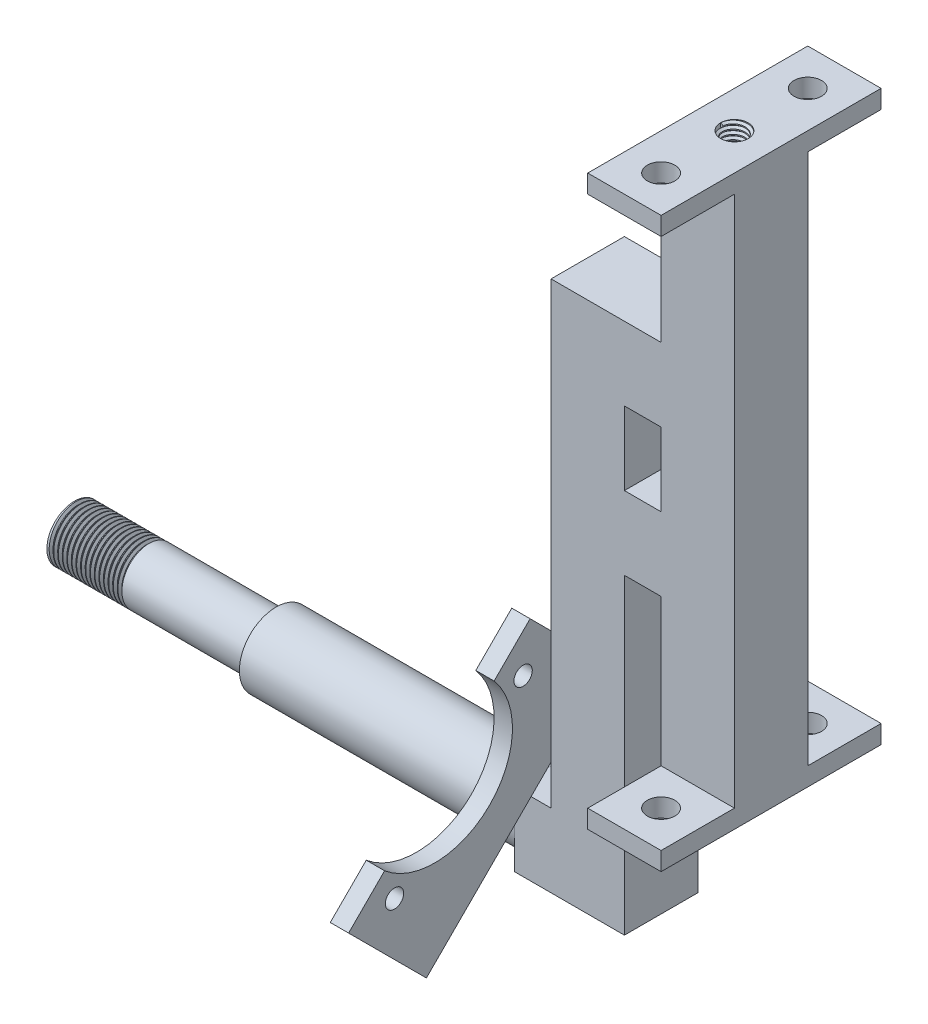
SolidWorks part; units mm, degrees
material "Plain Carbon Steel"
ref_plane "Front Plane" through (0, 0, 0) normal (0, 0, 1) x (1, 0, 0)
ref_plane "Top Plane" through (0, 0, 0) normal (0, 1, 0) x (1, 0, 0)
ref_plane "Right Plane" through (0, 0, 0) normal (1, 0, 0) x (0, 0, -1)
sketch "Sketch1" plane through (0, 0, 0) normal (0, 1, 0) x (1, 0, 0)
  line L1 (12.7, -12.7) -> (-12.7, -12.7)
  line L2 (12.7, -12.7) -> (12.7, 12.7)
  line L3 (12.7, 12.7) -> (-12.7, 12.7)
  line L4 (-12.7, -12.7) -> (-12.7, 12.7)
  line L5 (12.7, -12.7) -> (-12.7, 12.7) construction
  line L6 (12.7, 12.7) -> (-12.7, -12.7) construction
  line L7 (10.16, -10.16) -> (-10.16, -10.16)
  line L8 (10.16, -10.16) -> (10.16, 10.16)
  line L9 (10.16, 10.16) -> (-10.16, 10.16)
  line L10 (-10.16, -10.16) -> (-10.16, 10.16)
  line L11 (10.16, -10.16) -> (-10.16, 10.16) construction
  line L12 (10.16, 10.16) -> (-10.16, -10.16) construction
  point P0 (0, 0)
  point P5 (0, 0)
  dimension "D1" = 2.54
  dimension "1" = 25.4
extrude "Sq_Tb Extrude" add sketch "Sketch1" along normal blind 196.85
sketch "Sketch3" plane through (0, 196.85, 0) normal (0, 1, 0) x (1, 0, 0)
  line L0 (12.7, -12.7) -> (12.7, 12.7) construction
  line L1 (10.16, -10.16) -> (-10.16, -10.16)
  line L2 (10.16, -10.16) -> (10.16, 10.16)
  line L3 (10.16, 10.16) -> (-10.16, 10.16)
  line L4 (-10.16, -10.16) -> (-10.16, 10.16)
  line L5 (10.16, -10.16) -> (-10.16, 10.16) construction
  line L6 (10.16, 10.16) -> (-10.16, -10.16) construction
  line L7 (-12.7, 12.7) -> (12.7, 12.7)
  line L8 (-12.7, 12.7) -> (-12.7, 38.1)
  line L9 (-12.7, 38.1) -> (12.7, 38.1)
  line L10 (12.7, 12.7) -> (12.7, 38.1)
  line L11 (-12.7, 12.7) -> (12.7, 38.1) construction
  line L12 (-12.7, 38.1) -> (12.7, 12.7) construction
  line L13 (0, 0) -> (12.7, 0) construction
  line L14 (-12.7, -38.1) -> (12.7, -12.7) construction
  line L15 (-12.7, -12.7) -> (12.7, -38.1) construction
  line L16 (12.7, -12.7) -> (12.7, -38.1)
  line L17 (-12.7, -38.1) -> (12.7, -38.1)
  line L18 (-12.7, -12.7) -> (-12.7, -38.1)
  line L19 (-12.7, -12.7) -> (12.7, -12.7)
  circle A0 centre (0, 0) radius 4.7625
  circle A1 centre (0, 25.4) radius 4.7625
  circle A2 centre (0, -25.4) radius 4.7625
  point P0 (0, 0)
  point P13 (0, 25.4)
  point P26 (0, -25.4)
  dimension "D1" = 9.525
  dimension "D3" = 50.8
  dimension "D2" = 25.4
extrude "End Caps" add sketch "Sketch3" against normal blind 6.35
ref_plane "Mid-Plane" through (0, 98.425, 0) normal (0, 1, 0) x (1, 0, 0)
mirror "End Cap Mirror" about plane through (0, 98.425, 0) normal (0, 1, 0) of "End Caps"
thread "Top Thread" pitch 1.5875 method extrude profile "Thread Profile1" start angle 0, offset 0, length 0, pitch 1.5875, diameter 9.525
ref_plane "Plane2" through (-4.7625, 196.85, 0) normal (0, 0, 1) x (-1, 0, 0)
sketch "Thread Profile1" plane through (-4.7625, 196.85, 0) normal (0, 0, 1) x (-1, 0, 0)
  line L0 (0, 0) -> (0, 1.5875) construction
  line L11 (0, 0) -> (0, 1.3891)
  line L12 (0, 1.3891) -> (-0.8593, 0.893)
  line L13 (-0.8593, 0.893) -> (-0.8593, 0.4961)
  line L15 (-0.8593, 0.4961) -> (0, 0)
  line L17 (-0.8593, 0.6945) -> (0, 0.6945) construction
  point P2 (0, 0)
  dimension "Pitch" = 1.5875
  dimension "Profile_Angle" = 60
  dimension "Profile_Land" = 0.3969
  dimension "Profile_Height" = 0.8593
thread "Bottom Thread" pitch 1.5875 method extrude profile "Thread Profile2" start angle 0, offset 0, length 0, pitch 1.5875, diameter 9.525
ref_plane "Plane3" through (4.7625, 0, 0) normal (0, 0, 1) x (1, 0, 0)
sketch "Thread Profile2" plane through (4.7625, 0, 0) normal (0, 0, 1) x (1, 0, 0)
  line L0 (0, 0) -> (0, 1.5875) construction
  line L11 (0, 0) -> (0, 1.3891)
  line L12 (0, 1.3891) -> (-0.8593, 0.893)
  line L13 (-0.8593, 0.893) -> (-0.8593, 0.4961)
  line L15 (-0.8593, 0.4961) -> (0, 0)
  line L17 (-0.8593, 0.6945) -> (0, 0.6945) construction
  point P2 (0, 0)
  dimension "Pitch" = 1.5875
  dimension "Profile_Angle" = 60
  dimension "Profile_Land" = 0.3969
  dimension "Profile_Height" = 0.8593
sketch "Sketch9" plane through (0, 0, 0) normal (0, 0, 1) x (1, 0, 0)
  line L1 (-12.7, 190.5) -> (-12.7, 6.35) construction
  line L11 (-25.4, -50.8) -> (-63.5, -50.8)
  line L12 (-63.5, -50.8) -> (-63.5, -25.4)
  line L13 (-63.5, -25.4) -> (-63.1415, -25.4)
  line L15 (-63.5, -38.1) -> (0, -38.1) construction
  line L16 (0, -38.1) -> (0, 0) construction
  line L24 (-25.4, -25.4) -> (-25.4, -50.8)
  line L27 (-25.4, 107.95) -> (-50.8, 107.95) construction
  line L28 (-50.8, 107.95) -> (-50.8, -25.4)
  line L29 (-50.8, 107.95) -> (-50.8, 133.35)
  line L30 (-50.8, 133.35) -> (-12.7, 133.35)
  line L31 (-12.7, 190.5) -> (-12.7, 6.35) construction
  line L32 (-25.4, 107.95) -> (-12.7, 107.95)
  line L33 (-25.4, 57.15) -> (-12.7, 57.15)
  line L34 (-25.4, 82.55) -> (-12.7, 82.55)
  line L35 (-19.05, 82.55) -> (-19.05, 57.15) construction
  line L36 (-25.4, 107.95) -> (-50.8, 133.35) construction
  line L37 (-63.1415, -25.4) -> (-50.8, -25.4)
  line L38 (-50.8, -25.4) -> (-25.4, -25.4) construction
  line L39 (-50.8, -25.4) -> (-25.4, -50.8) construction
  line L40 (-12.7, 133.35) -> (-12.7, 107.95)
  line L41 (12.7, 190.5) -> (-12.7, 190.5) construction
  line L42 (-12.7, 0) -> (12.7, 0) construction
  line L43 (-25.4, 107.95) -> (-25.4, 82.55)
  line L44 (-25.4, 57.15) -> (-25.4, -25.4)
  line L45 (-12.7, 82.55) -> (-12.7, 57.15)
  dimension "D1" = 25.4
  dimension "D2" = 50.8
  dimension "D3" = 25.4
  dimension "D4" = 57.15
  dimension "D5" = 57.15
  dimension "D6" = 50.8
  dimension "D8" = 38.1
extrude "Sq_Tb Angles" add sketch "Sketch9" along normal blind 12.7 and the other way blind 12.7 contours L13 L12 L11 region at (-37.0114, 42.9079, 0)
sketch "Sketch11" plane through (0, 0, 0) normal (0, 0, 1) x (1, 0, 0)
  line L0 (-63.5, -38.1) -> (-228.6, -38.1)
  line L1 (-63.5, -50.8) -> (-63.5, -25.4) construction
  line L2 (-228.6, -38.1) -> (-228.6, -28.575)
  line L3 (-228.6, -28.575) -> (-158.75, -28.575)
  line L4 (-158.75, -28.575) -> (-158.75, -25.4)
  line L5 (-158.75, -25.4) -> (-63.5, -25.4)
  line L6 (-63.5, -25.4) -> (-63.5, -38.1)
  dimension "D1" = 12.7
  dimension "D2" = 9.525
  dimension "D3" = 95.25
  dimension "D4" = 69.85
revolve "Wheel Rod" add sketch "Sketch11" angle 360 about L0
thread "Wheel Threads" pitch 1.5875 method cut profile "Thread Profile3" start angle 0, offset 0, length 25.4, pitch 1.5875, diameter 19.05
ref_plane "Plane4" through (-228.6, -38.1, -9.525) normal (0, -1, 0) x (0, 0, -1)
sketch "Thread Profile3" plane through (-228.6, -38.1, -9.525) normal (0, -1, 0) x (0, 0, -1)
  line L0 (0, 0) -> (0, 1.5875) construction
  line L11 (0, 0) -> (0, 1.3891)
  line L12 (0, 1.3891) -> (-0.8593, 0.893)
  line L13 (-0.8593, 0.893) -> (-0.8593, 0.4961)
  line L15 (-0.8593, 0.4961) -> (0, 0)
  line L17 (-0.8593, 0.6945) -> (0, 0.6945) construction
  point P2 (0, 0)
  dimension "Pitch" = 1.5875
  dimension "Profile_Angle" = 60
  dimension "Profile_Land" = 0.3969
  dimension "Profile_Height" = 0.8593
ref_plane "Tie-Rod Mount Plane" through (0, 44.45, 0) normal (0, 1, 0) x (1, 0, 0)
sketch "Sketch12" plane through (-50.8, 0, 0) normal (-1, 0, 0) x (0, 0, 1)
  line L0 (70.3677, -15.3502) -> (82.8271, -27.8097)
  line L1 (82.8271, -27.8097) -> (55.8864, -54.7505)
  line L2 (55.8864, -54.7505) -> (-6.9754, 8.1113)
  line L3 (24.4555, -23.3196) -> (36.2877, -11.4874) construction
  line L4 (19.9653, 35.0521) -> (-6.9754, 8.1113)
  line L5 (32.4248, 22.5926) -> (19.9653, 35.0521)
  line L6 (32.4248, 22.5926) -> (70.3677, -15.3502)
  line L7 (22.3872, 19.1599) -> (66.9349, -25.3879) construction
  line L8 (24.4555, -23.3196) -> (44.661, -3.114) construction
  line L9 (52.9971, 5.2221) -> (51.3962, 3.6212) construction
  line L11 (12.7, -25.4) -> (12.7, 133.35) construction
  circle A0 centre (66.9349, -25.3879) radius 3.175
  circle A1 centre (22.3872, 19.1599) radius 3.175
  arc A2 (70.3677, -15.3502) -> (32.4248, 22.5926) centre (52.9971, 5.2221) cw
  circle A3 centre (0, -38.1) radius 28.575 construction
  point P11 (66.9349, -25.3879)
  point P14 (0, 0)
  point P16 (-30.1549, 24.7423)
  point P19 (52.1215, 27.526)
  point P22 (68.9055, -23.3196)
  line M12 (12.7, -25.4) -> (12.7, 133.35)
  dimension "D2" = 6.35
  dimension "D3" = 26.925
  dimension "D9" = 57.15
  dimension "D1" = 63
  dimension "D4" = 38.1
  dimension "D5" = 88.9
  dimension "D6" = 16.7333
  dimension "D7" = 28.575
  dimension "D8" = 2.264
  dimension "D10" = 135
extrude "Boss-Extrude1" add sketch "Sketch12" along normal blind 6.35 contours L0 A2 L5 L4 L2 L1 A1 A0 M12 | L4 L2 M12 region at (-50.8, -22.3857, 75.7917) region at (-50.8, 8.1113, 6.1415)
